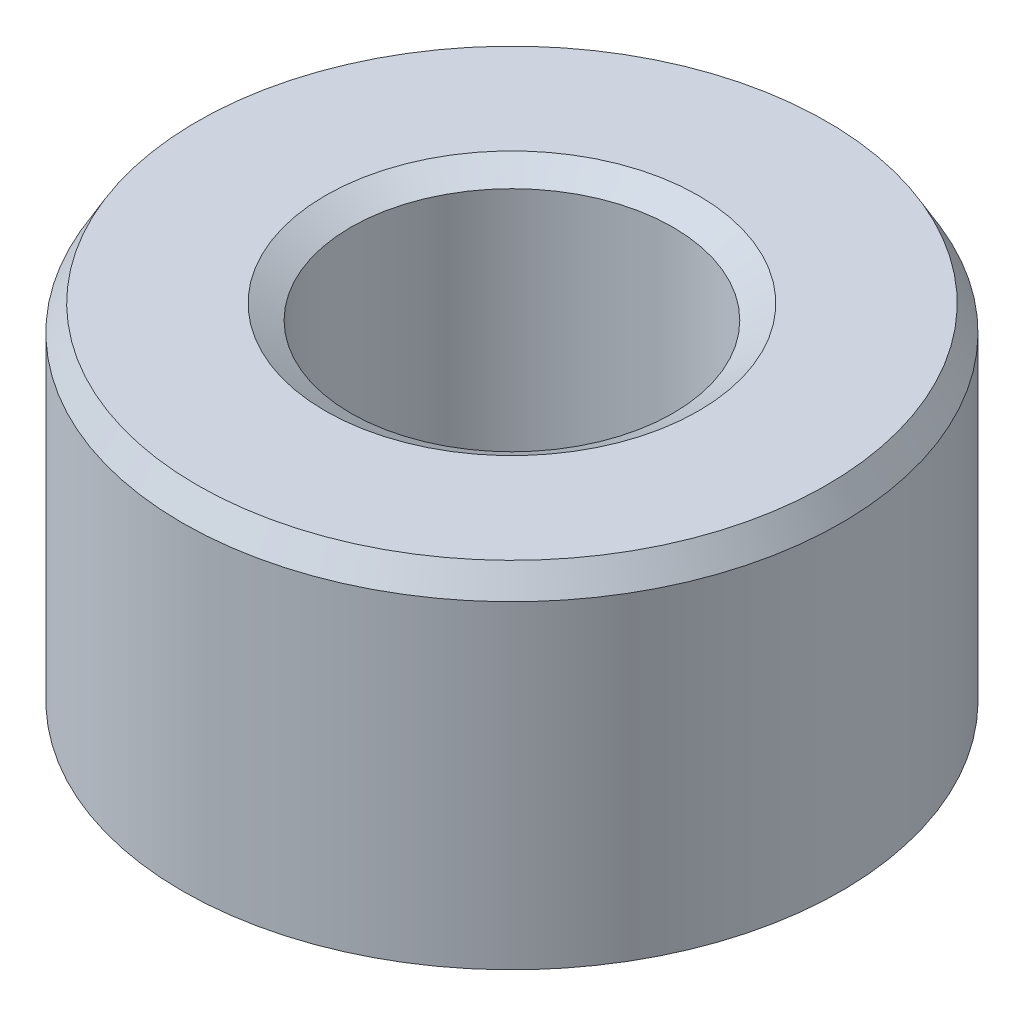
SolidWorks part; units mm, degrees
ref_plane "Front Plane" through (0, 0, 0) normal (0, 0, 1) x (1, 0, 0)
ref_plane "Top Plane" through (0, 0, 0) normal (0, 1, 0) x (1, 0, 0)
ref_plane "Right Plane" through (0, 0, 0) normal (1, 0, 0) x (0, 0, -1)
sketch "Sketch1" plane through (0, 0, 0) normal (0, 1, 0) x (1, 0, 0)
  circle A0 centre (0, 0) radius 30
  dimension "SLEEVE_OD" = 60
extrude "Boss-Extrude1" add sketch "Sketch1" along normal blind 32.6712
sketch "Sketch2" plane through (0, 0, 0) normal (0, 1, 0) x (1, 0, 0)
  circle A0 centre (0, 0) radius 14.667
  dimension "BORE_D" = 29.334
extrude "Cut-Extrude1" cut sketch "Sketch2" along normal through all
chamfer "Chamfer1" distance 2.3183 angle 30 4 edges at (0, 32.6712, 14.667) (0, 0, 14.667) (0, 0, 30) (0, 32.6712, 30) first distance on face at (0, 32.6712, 14.667) first distance on face at (0, 0, 14.667) first distance on face at (0, 32.6712, 30)
